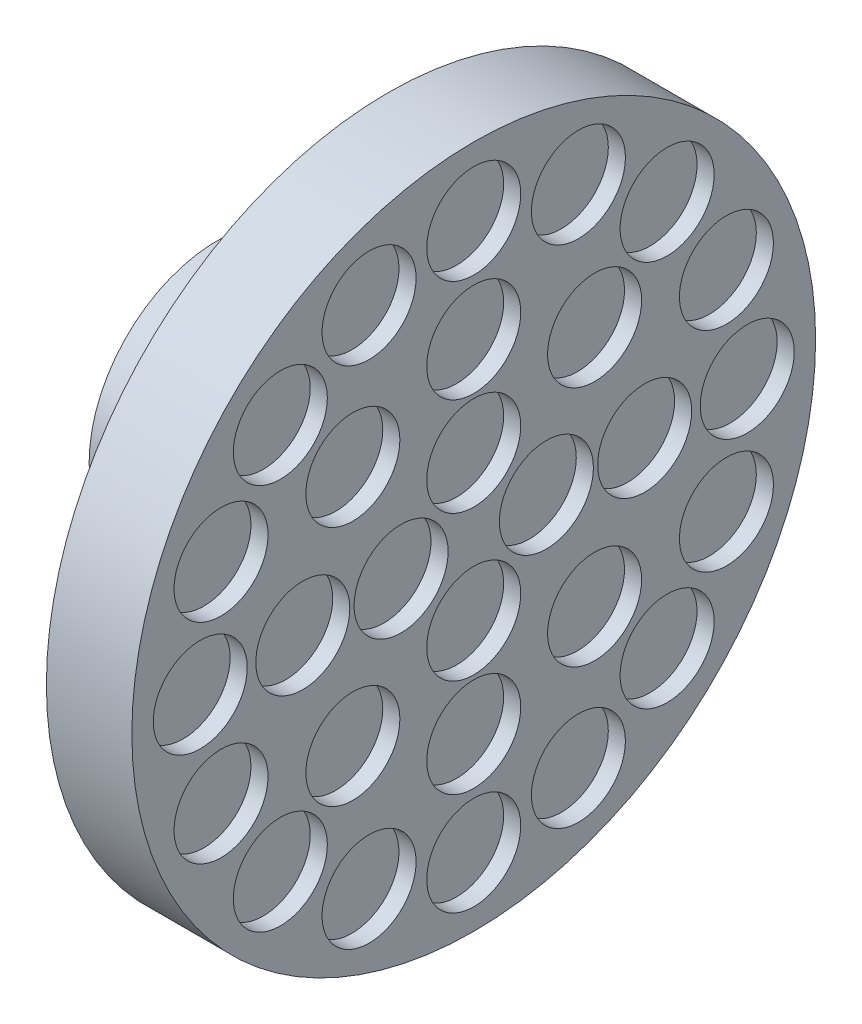
SolidWorks part; units mm, degrees
ref_plane "Plan de face" through (0, 0, 0) normal (1, 0, 0) x (0, 1, 0)
ref_plane "Plan de dessus" through (0, 0, 0) normal (0, 0, 1) x (0, 1, 0)
ref_plane "Plan de droite" through (0, 0, 0) normal (0, 1, 0) x (-1, 0, 0)
sketch "Esquisse1" plane through (0, 0, 0) normal (1, 0, 0) x (0, 1, 0)
  circle A0 centre (0, 0) radius 40
  dimension "D1" = 80
extrude "Boss.-Extru.2" add sketch "Esquisse1" along normal blind 10 contours A0
sketch "Esquisse5" plane through (10, 0, 0) normal (1, 0, 0) x (0, 1, 0)
  circle A0 centre (0, 32) radius 5.5
  circle A1 centre (12.2459, 29.5641) radius 5.5
  circle A2 centre (22.6274, 22.6274) radius 5.5
  circle A3 centre (29.5641, 12.2459) radius 5.5
  circle A4 centre (32, 0) radius 5.5
  circle A5 centre (29.5641, -12.2459) radius 5.5
  circle A6 centre (22.6274, -22.6274) radius 5.5
  circle A7 centre (12.2459, -29.5641) radius 5.5
  circle A8 centre (0, -32) radius 5.5
  circle A9 centre (-12.2459, -29.5641) radius 5.5
  circle A10 centre (-22.6274, -22.6274) radius 5.5
  circle A11 centre (-29.5641, -12.2459) radius 5.5
  circle A12 centre (-32, 0) radius 5.5
  circle A13 centre (-29.5641, 12.2459) radius 5.5
  circle A14 centre (-22.6274, 22.6274) radius 5.5
  circle A15 centre (-12.2459, 29.5641) radius 5.5
  circle A16 centre (0, 20) radius 5.5
  circle A17 centre (14.1421, 14.1421) radius 5.5
  circle A18 centre (20, 0) radius 5.5
  circle A19 centre (14.1421, -14.1421) radius 5.5
  circle A20 centre (0, -20) radius 5.5
  circle A21 centre (-14.1421, -14.1421) radius 5.5
  circle A22 centre (-20, 0) radius 5.5
  circle A23 centre (-14.1421, 14.1421) radius 5.5
  circle A24 centre (0, 8.5) radius 5.5
  circle A25 centre (8.5, 0) radius 5.5
  circle A26 centre (0, -8.5) radius 5.5
  circle A27 centre (-8.5, 0) radius 5.5
  point P35 (0, 0)
  point P52 (0, 0)
  point P62 (0, 0)
  dimension "D1" = 11
  dimension "D4" = 11
  dimension "D7" = 11
  dimension "D2" = 32
  dimension "D5" = 20
  dimension "D8" = 8.5
  dimension "D3" = 16
  dimension "D6" = 8
  dimension "D9" = 4
extrude "Enlèv. mat.-Extru.2" cut sketch "Esquisse5" against normal blind 2
sketch "Esquisse6" plane through (0, 0, 0) normal (-1, 0, 0) x (0, -1, 0)
  circle A0 centre (0, 0) radius 15
  dimension "D1" = 30
extrude "Boss.-Extru.3" add sketch "Esquisse6" along normal blind 20
fillet "Congé1" radius 10 1 edges at (0, 0, 15)
sketch "Esquisse7" plane through (-20, 0, 0) normal (-1, 0, 0) x (0, 0, 1)
  circle A0 centre (0, 0) radius 5
  dimension "D1" = 10
extrude "Enlèv. mat.-Extru.3" cut sketch "Esquisse7" against normal blind 16
sketch "Esquisse8" plane through (10, 0, 0) normal (1, 0, 0) x (0, 0, -1)
  line L0 (-32, 0) -> (32, 0) construction
